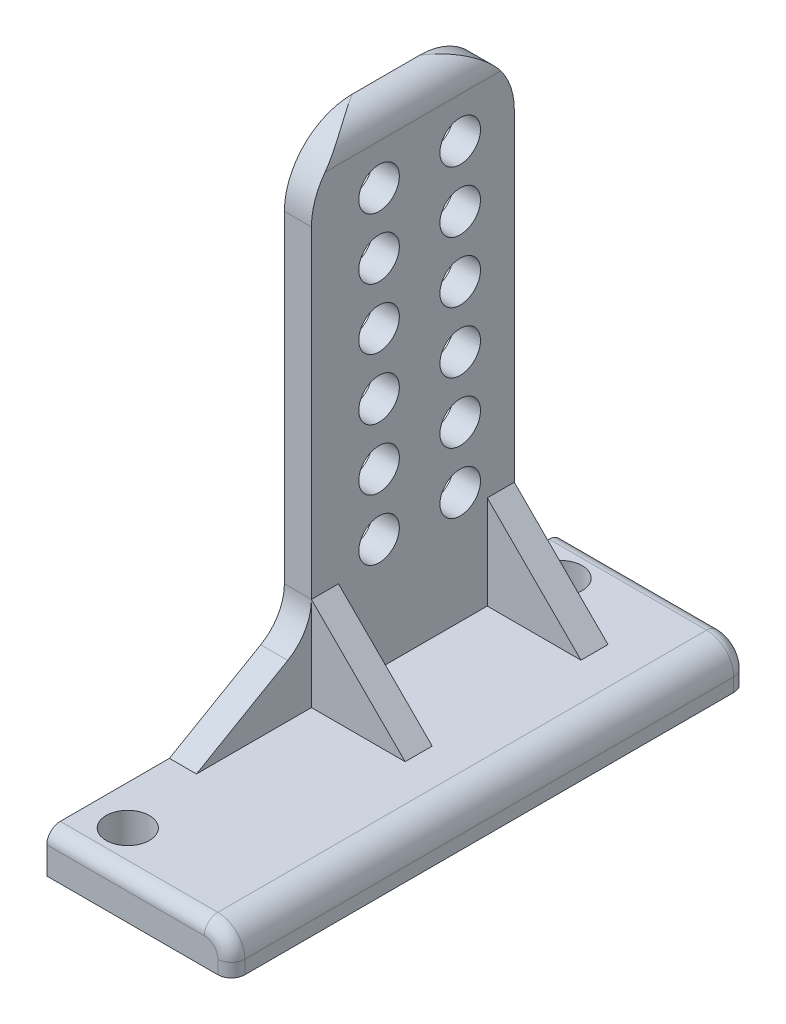
SolidWorks part; units mm, degrees
ref_plane "前视基准面" through (0, 0, 0) normal (0, 0, 1) x (1, 0, 0)
ref_plane "上视基准面" through (0, 0, 0) normal (0, 1, 0) x (1, 0, 0)
ref_plane "右视基准面" through (0, 0, 0) normal (1, 0, 0) x (0, 0, -1)
sketch "草图1" plane through (0, 0, 0) normal (1, 0, 0) x (0, 0, -1)
  line L2 (4.9848, 3.7736) -> (12.5891, 3.7736) construction
  line L4 (8.5, 6.9282) -> (8.5, 30.7736)
  line L5 (13.5, 35.7736) -> (18.5, 35.7736)
  line L8 (6.75, 3.8971) -> (0, 0)
  line L9 (0, 0) -> (23.5, 0)
  line L12 (23.5, 30.7736) -> (23.5, 0)
  arc A2 (8.5, 6.9282) -> (6.75, 3.8971) centre (5, 6.9282) cw
  arc A3 (8.5, 30.7736) -> (13.5, 35.7736) centre (13.5, 30.7736) cw
  arc A4 (18.5, 35.7736) -> (23.5, 30.7736) centre (18.5, 30.7736) cw
  circle A5 centre (19.5, 30.7736) radius 1.5
  circle A7 centre (13.5, 30.7736) radius 1.5
  circle A8 centre (19.5, 26.2736) radius 1.5
  circle A9 centre (13.5, 26.2736) radius 1.5
  circle A10 centre (19.5, 21.7736) radius 1.5
  circle A11 centre (13.5, 21.7736) radius 1.5
  circle A12 centre (19.5, 17.2736) radius 1.5
  circle A13 centre (13.5, 17.2736) radius 1.5
  circle A14 centre (19.5, 12.7736) radius 1.5
  circle A15 centre (13.5, 12.7736) radius 1.5
  circle A16 centre (19.5, 8.2736) radius 1.5
  circle A17 centre (13.5, 8.2736) radius 1.5
  circle A20 centre (19.5, 3.7736) radius 1.5 [skipped]
  circle A21 centre (13.5, 3.7736) radius 1.5 [skipped]
  point P1 (0, 0)
  point P2 (0, 0)
  dimension "D2" = 27
  dimension "D3" = 5
  dimension "D7" = 3
  dimension "D8" = 3.5
  dimension "D9" = 7
  dimension "D10" = 3
  dimension "D11" = 3
  dimension "D4" = 10
  dimension "D5" = 30
  dimension "D6" = 8.5
  dimension "D12" = 30.7736
extrude "凸台-拉伸1" add sketch "草图1" along normal blind 2
fillet "圆角1" radius 2 1 edges at (2, 35.7736, -16) tangent propagation no
sketch "草图2" plane through (0, 0, 0) normal (0, -1, 0) x (1, 0, 0)
  line L0 (2, -8.5) -> (0, -8.5) construction
  line L1 (0, 9.07) -> (13.65, 9.07)
  line L2 (0, 9.07) -> (0, -29.07)
  line L3 (0, -29.07) -> (13.65, -29.07)
  line L4 (13.65, 9.07) -> (13.65, -29.07)
  line L5 (2, -23.5) -> (0, -23.5) construction
  line L6 (0, 0) -> (0, -23.5) construction
  point P6 (1, -8.5)
  point P9 (20.7371, 22.57)
  dimension "D1" = 17.57
  dimension "D2" = 5.57
  dimension "D3" = 13.65
extrude "凸台-拉伸2" add sketch "草图2" along normal blind 3
sketch "草图5" plane through (0, -3, 0) normal (0, -1, 0) x (1, 0, 0)
  line L0 (13.65, 9.07) -> (0, 9.07) construction
  line L1 (0, -10) -> (13.65, -10) construction
  line L2 (13.65, -29.07) -> (13.65, 9.07) construction
  line L4 (0, 9.07) -> (0, -29.07) construction
  circle A0 centre (2.92, 6) radius 1.6
  circle A1 centre (2.92, -26) radius 1.6
  dimension "D1" = 3.07
  dimension "D3" = 3.2
  dimension "D2" = 2.92
extrude "切除-拉伸1" cut sketch "草图5" against normal through all
fillet "圆角5" radius 2 1 edges at (13.65, 0, -10)
fillet "圆角6" radius 1 6 edges at (13.65, -2.5, -29.07) (13.0642, -0.5858, -29.07) (13.65, -2.5, 9.07) (13.0642, -0.5858, 9.07) (5.825, 0, -29.07) (5.825, 0, 9.07)
sketch "草图6" plane through (0, 0, -8.5) normal (0, 0, 1) x (1, 0, 0)
  line L1 (2, 6.9282) -> (8.9282, 0)
  line L2 (0, 0) -> (11.65, 0) construction
  dimension "D1" = 45
rib "筋5" sketch "草图6" sketch "草图6" thickness 2 extrusion direction parallel to sketch draft on no parameters "D1"=2
sketch "草图8" plane through (0, 0, -23.5) normal (0, 0, -1) x (-1, 0, 0)
  line L0 (-2, 6.9282) -> (-8.9282, 0)
  line L1 (-11.65, 0) -> (0, 0) construction
  line L2 (-2, 6.9282) -> (-8.9282, 0) construction
  point P7 (-2, 3.4282)
rib "筋8" sketch "草图8" sketch "草图8" thickness 2 extrusion direction parallel to sketch draft on no parameters "D1"=2
